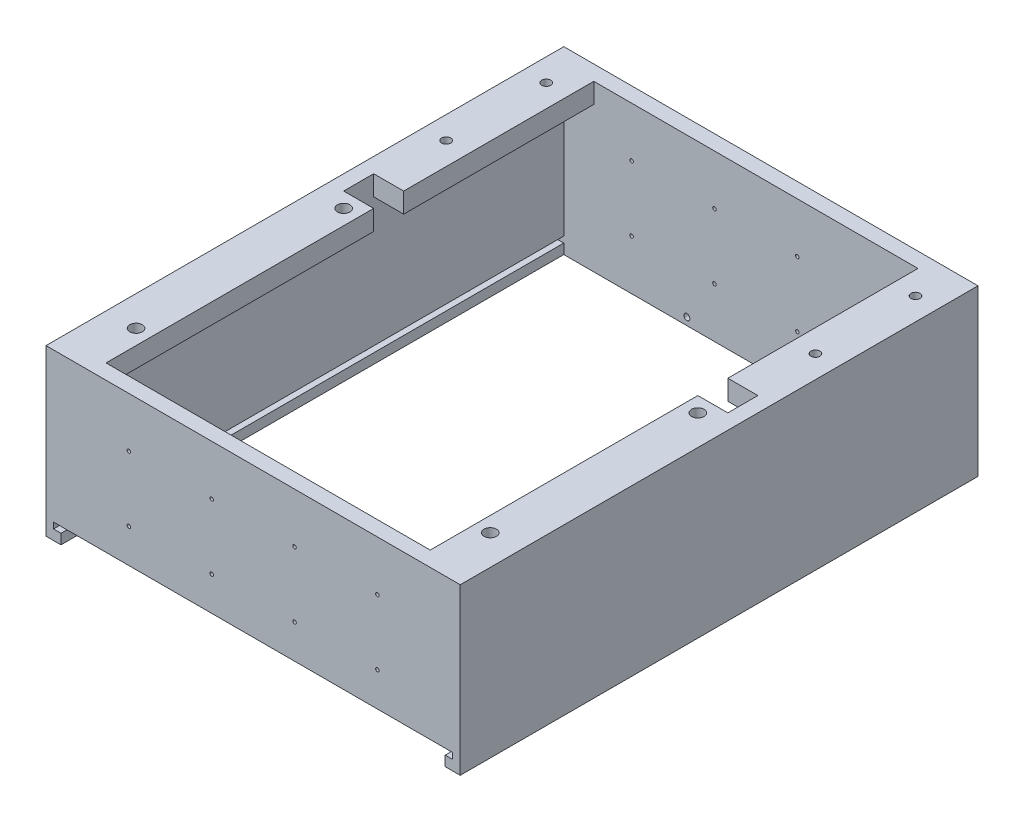
SolidWorks part; units mm, degrees
ref_plane "前视基准面" through (0, 0, 0) normal (0, 0, 1) x (1, 0, 0)
ref_plane "上视基准面" through (0, 0, 0) normal (0, 1, 0) x (1, 0, 0)
ref_plane "右视基准面" through (0, 0, 0) normal (1, 0, 0) x (0, 0, -1)
other "Configuration Table"
sketch "草图1" plane through (0, 0, 0) normal (0, 1, 0) x (1, 0, 0)
  line L0 (-35.4, 20.75) -> (-35.4, -20.75) construction
  line L5 (-38.4, 23.75) -> (-32.4, 23.75)
  line L6 (-38.4, 23.75) -> (-38.4, -23.75)
  line L7 (-38.4, -23.75) -> (-32.4, -23.75)
  line L8 (-32.4, 23.75) -> (-32.4, -23.75)
  line L13 (-35.4, -20.75) -> (-35.4, -23.75) construction
  line L14 (-35.4, 20.75) -> (-35.4, 23.75) construction
  line L16 (-32.4, -23.75) -> (-38.4, -23.75)
  line L17 (-32.4, -23.75) -> (-32.4, -32.75)
  line L18 (-32.4, -32.75) -> (-38.4, -32.75)
  line L19 (-38.4, -23.75) -> (-38.4, -32.75)
  line L20 (-38.4, 67.75) -> (-32.4, 67.75)
  line L21 (-38.4, 67.75) -> (-38.4, 29.75)
  line L22 (-38.4, 29.75) -> (-32.4, 29.75)
  line L23 (-32.4, 67.75) -> (-32.4, 29.75)
  line L24 (-38.4, 67.75) -> (-32.4, 67.75)
  line L25 (-38.4, 67.75) -> (-38.4, 70.75)
  line L26 (-38.4, 70.75) -> (-32.4, 70.75)
  line L27 (-32.4, 67.75) -> (-32.4, 70.75)
  line L28 (-38.4, -32.75) -> (-32.4, -32.75)
  line L29 (-38.4, -32.75) -> (-38.4, -29.75)
  line L30 (-38.4, -29.75) -> (-32.4, -29.75)
  line L31 (-32.4, -32.75) -> (-32.4, -29.75)
  circle A8 centre (-35.4, 20.75) radius 1.25
  circle A9 centre (-35.4, -20.75) radius 1.25
  circle A12 centre (-35.4, 20.75) radius 2
  circle A13 centre (-35.4, -20.75) radius 2
  point P4 (-38.4, 0)
  dimension "D3" = 6
  dimension "D4" = 41.5
  dimension "D1" = 2.5
  dimension "D2" = 4
  dimension "D5" = 3
  dimension "D6" = 9
  dimension "D7" = 35.4
  dimension "D8" = 6
  dimension "D9" = 38
  dimension "D10" = 3
  dimension "D11" = 3
extrude "凸台-拉伸1" add sketch "草图1" along normal blind 4 contours L8 L5 L6 L7 A13 A12 | A12 A8 | A13 A9 | L20 L27 L26 L25 | L7 L19 L18 L17 | L21 L22 L23 L20 | L29 L28 L31 L30 region at (-35.4, 0, 0) region at (-35.4, 0, 26.75) region at (-35.4, 0, -69.25) region at (-37.3434, 0, -20.75) region at (-37.3434, 0, 20.75)
sketch "草图3" plane through (0, 4, 0) normal (0, 1, 0) x (1, 0, 0)
  line L0 (-38.4, 70.75) -> (-38.4, 29.75) construction
  line L1 (-38.4, 70.75) -> (-41.4, 70.75)
  line L2 (-38.4, 70.75) -> (-38.4, -32.75)
  line L3 (-38.4, -32.75) -> (-41.4, -32.75)
  line L4 (-41.4, 70.75) -> (-41.4, -32.75)
  line L5 (-38.4, -32.75) -> (-32.4, -32.75) construction
  dimension "D1" = 3
extrude "凸台-拉伸2" add sketch "草图3" against normal blind 33
extrude "切除-拉伸1" cut sketch "草图1<5>" along normal blind 1.5 contours A12 | A13
sketch "草图1<5>" plane through (0, 0, 0) normal (0, 1, 0) x (1, 0, 0) same geometry as "草图1"
mirror "镜向3" about plane through (0, 0, 0) normal (1, 0, 0) of bodies 167
sketch "草图4" plane through (0, 4, 0) normal (0, -1, 0) x (1, 0, 0)
  line L0 (41.4, -70.75) -> (41.4, 32.75) construction
  line L1 (41.4, 32.75) -> (-41.4, 32.75)
  line L2 (41.4, 32.75) -> (41.4, 29.75)
  line L3 (41.4, 29.75) -> (-41.4, 29.75)
  line L4 (-41.4, 32.75) -> (-41.4, 29.75)
  line L5 (41.4, 32.75) -> (38.4, 32.75) construction
  line L6 (-41.4, -70.75) -> (-41.4, 32.75) construction
  line L8 (41.4, -70.75) -> (-41.4, -70.75)
  line L9 (41.4, -70.75) -> (41.4, -67.75)
  line L10 (41.4, -67.75) -> (-41.4, -67.75)
  line L11 (-41.4, -70.75) -> (-41.4, -67.75)
  dimension "D1" = 3
extrude "凸台-拉伸3" add sketch "草图4" along normal up to surface (33 mm away) up to face at (39.9, -29, -19)
sketch "草图5" plane through (0, -29, 0) normal (0, -1, 0) x (1, 0, 0)
  line L0 (38.4, 29.75) -> (38.4, -67.75) construction
  line L1 (38.4, 29.75) -> (-38.4, 29.75)
  line L2 (38.4, 29.75) -> (38.4, 32.75)
  line L3 (38.4, 32.75) -> (-38.4, 32.75)
  line L4 (-38.4, 29.75) -> (-38.4, 32.75)
  line L5 (-38.4, 29.75) -> (38.4, 29.75) construction
  line L6 (-41.4, 32.75) -> (41.4, 32.75) construction
  line L7 (-38.4, 29.75) -> (-38.4, -67.75) construction
extrude "切除-拉伸2" cut sketch "草图5" against normal blind 3.2
sketch "草图7" plane through (0, 0, -67.75) normal (0, 0, 1) x (1, 0, 0)
  line L0 (38.4, -25.8) -> (38.4, -29) construction
  line L1 (-39.9, -25.8) -> (39.9, -25.8)
  line L2 (-39.9, -25.8) -> (-39.9, -27)
  line L3 (-39.9, -27) -> (39.9, -27)
  line L4 (39.9, -25.8) -> (39.9, -27)
  line L6 (-38.4, -29) -> (-38.4, 0) construction
  line L7 (38.4, -25.8) -> (-38.4, -25.8) construction
  dimension "D1" = 1.5
  dimension "D2" = 1.5
  dimension "D3" = 1.2
extrude "切除-拉伸4" cut sketch "草图7" along normal through all
sketch "草图8" plane through (0, 4, 0) normal (0, 1, 0) x (1, 0, 0)
  line L0 (41.4, 62.75) -> (32.4, 62.75) construction
  line L1 (41.4, 70.75) -> (41.4, -32.75) construction
  line L2 (32.4, 67.75) -> (32.4, 29.75) construction
  line L3 (-32.4, 62.75) -> (-41.4, 62.75) construction
  line L4 (-32.4, 67.75) -> (-32.4, 29.75) construction
  line L5 (-41.4, 70.75) -> (-41.4, -32.75) construction
  line L6 (41.4, 70.75) -> (-41.4, 70.75) construction
  circle A0 centre (36.9, 62.75) radius 0.9
  circle A1 centre (-36.9, 62.75) radius 0.9
  circle A2 centre (-36.9, 42.75) radius 0.9
  circle A3 centre (36.9, 42.75) radius 0.9
  dimension "D1" = 1.8
  dimension "D2" = 8
  dimension "D3" = 20
extrude "切除-拉伸5" cut sketch "草图8" against normal through all
sketch "草图9" plane through (0, 0, -70.75) normal (0, 0, -1) x (-1, 0, 0)
  line L0 (-41.4, -29) -> (41.4, -29) construction
  line L1 (41.4, -27.5) -> (13.8, -27.5) construction
  line L2 (41.4, -29) -> (41.4, 4) construction
  line L3 (-13.8, -27.5) -> (13.8, -27.5) construction
  line L4 (-41.4, -27.5) -> (-13.8, -27.5) construction
  line L5 (-41.4, -29) -> (-41.4, 4) construction
  circle A0 centre (13.8, -27.5) radius 0.6
  circle A1 centre (-13.8, -27.5) radius 0.6
  circle A2 centre (-13.8, -27.5) radius 1
  circle A3 centre (13.8, -27.5) radius 1
  dimension "D1" = 1.2
  dimension "D3" = 2
  dimension "D2" = 1.5
extrude "切除-拉伸6" cut sketch "草图9" against normal through all contours A1 | A0
extrude "切除-拉伸7" cut sketch "草图9<3>" against normal blind 1.5 contours A3 | A2
sketch "草图9<3>" plane through (0, 0, -70.75) normal (0, 0, -1) x (-1, 0, 0) same geometry as "草图9"
sketch "草图10" plane through (0, -25.8, 0) normal (0, -1, 0) x (1, 0, 0)
  line L0 (-13.8, 29.75) -> (-13.8, 32.75) construction
  line L1 (-38.4, 29.75) -> (38.4, 29.75) construction
  line L2 (39.9, 32.75) -> (-39.9, 32.75) construction
  line L3 (-41.4, 31.25) -> (-13.8, 31.25) construction
  line L4 (-41.4, -70.75) -> (-41.4, 32.75) construction
  line L5 (-13.8, 31.25) -> (13.8, 31.25) construction
  line L6 (13.8, 31.25) -> (41.4, 31.25) construction
  line L7 (41.4, -70.75) -> (41.4, 32.75) construction
  circle A0 centre (-13.8, 31.25) radius 0.35
  circle A1 centre (13.8, 31.25) radius 0.35
  dimension "D1" = 0.7
extrude "切除-拉伸8" cut sketch "草图10" against normal blind 3
sketch "草图11" plane through (0, -29, 0) normal (0, -1, 0) x (1, 0, 0)
  line L0 (39.9, 32.75) -> (39.9, 12.05) construction
  line L1 (38.4, 32.75) -> (41.4, 32.75) construction
  line L2 (39.9, 12.05) -> (39.9, -8.65) construction
  line L3 (39.9, -8.65) -> (39.9, -29.35) construction
  line L4 (39.9, -29.35) -> (39.9, -50.05) construction
  line L5 (39.9, -50.05) -> (39.9, -70.75) construction
  line L6 (41.4, -70.75) -> (-41.4, -70.75) construction
  line L7 (-39.9, 32.75) -> (-39.9, 12.05) construction
  line L8 (-41.4, 32.75) -> (-38.4, 32.75) construction
  circle A0 centre (39.9, 12.05) radius 0.35
  circle A1 centre (39.9, -8.65) radius 0.35
  circle A2 centre (39.9, -29.35) radius 0.35
  circle A3 centre (39.9, -50.05) radius 0.35
  circle A4 centre (-39.9, 12.05) radius 0.35
  circle A5 centre (-39.9, -8.65) radius 0.35
  circle A6 centre (-39.9, -29.35) radius 0.35
  circle A7 centre (-39.9, -50.05) radius 0.35
  dimension "D1" = 0.7
extrude "切除-拉伸9" cut sketch "草图11" against normal blind 3
sketch "草图12" plane through (0, 0, -70.75) normal (0, 0, -1) x (-1, 0, 0)
  line L0 (-41.4, -6) -> (-24.84, -6) construction
  line L1 (-41.4, -29) -> (-41.4, 4) construction
  line L2 (-24.84, -6) -> (-8.28, -6) construction
  line L3 (-8.28, -6) -> (8.28, -6) construction
  line L4 (8.28, -6) -> (24.84, -6) construction
  line L5 (24.84, -6) -> (41.4, -6) construction
  line L6 (41.4, -29) -> (41.4, 4) construction
  line L7 (-41.4, 4) -> (41.4, 4) construction
  line L8 (-41.4, -29) -> (41.4, -29) construction
  circle A0 centre (-24.84, -6) radius 0.35
  circle A1 centre (-8.28, -6) radius 0.35
  circle A2 centre (8.28, -6) radius 0.35
  circle A3 centre (24.84, -6) radius 0.35
  circle A4 centre (-24.84, -19) radius 0.35
  circle A5 centre (-8.28, -19) radius 0.35
  circle A6 centre (8.28, -19) radius 0.35
  circle A7 centre (24.84, -19) radius 0.35
  point P24 (0, 0)
  point P25 (0, 0)
  point P26 (0, 0)
  point P27 (0, 0)
  point P28 (0, 0)
  point P29 (0, 0)
  dimension "D1" = 0.7
  dimension "D2" = 10
  dimension "D3" = 10
extrude "切除-拉伸10" cut sketch "草图12" against normal through all
